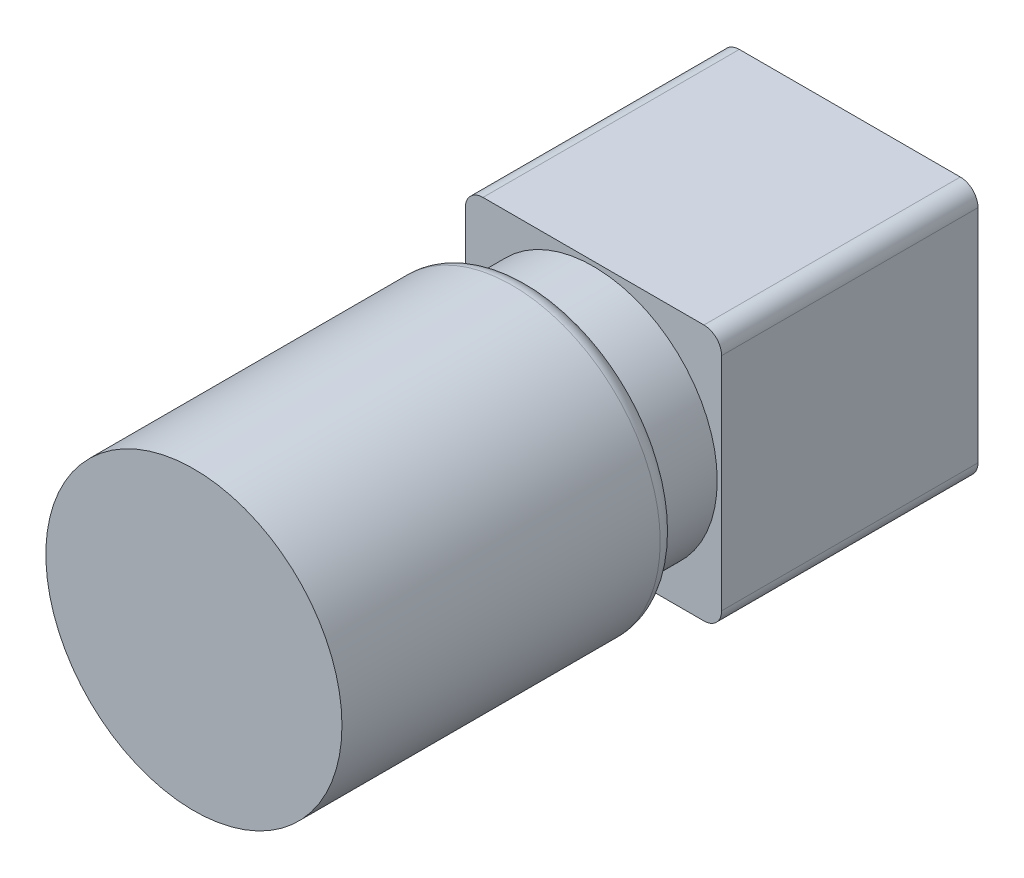
SolidWorks part; units mm, degrees
ref_plane "前视基准面" through (0, 0, 0) normal (0, 0, 1) x (1, 0, 0)
ref_plane "上视基准面" through (0, 0, 0) normal (0, 1, 0) x (1, 0, 0)
ref_plane "右视基准面" through (0, 0, 0) normal (1, 0, 0) x (0, 0, -1)
sketch "草图1" plane through (0, 0, 0) normal (0, 0, 1) x (1, 0, 0)
  line L1 (14.5, -14.5) -> (-14.5, -14.5)
  line L2 (14.5, -14.5) -> (14.5, 14.5)
  line L3 (14.5, 14.5) -> (-14.5, 14.5)
  line L4 (-14.5, -14.5) -> (-14.5, 14.5)
  line L5 (14.5, -14.5) -> (-14.5, 14.5) construction
  line L6 (14.5, 14.5) -> (-14.5, -14.5) construction
  point P0 (0, 0)
  dimension "D1" = 29
  dimension "D2" = 29
extrude "凸台-拉伸1" add sketch "草图1" along normal blind 29
sketch "草图2" plane through (0, 0, 29) normal (0, 0, 1) x (1, 0, 0)
  circle A0 centre (0, 0) radius 14
  dimension "D1" = 28
extrude "凸台-拉伸2" add sketch "草图2" along normal blind 7.2
sketch "草图3" plane through (0, -14.5, 0) normal (0, -1, 0) x (-1, 0, 0)
  line L0 (0, -29) -> (0, 0) construction
  line L2 (14.5, -29) -> (-14.5, -29) construction
  point P6 (0, -14.5)
hole_wizard "M3 螺纹孔1" positions "草图4" profile "草图5" tap size "M3" standard "GB"
sketch "草图4" plane through (0, -14.5, 0) normal (0, -1, 0) x (-1, 0, 0)
  line L0 (14.5, -29) -> (-14.5, -29) construction
  line L3 (0, -29) -> (0, 0) construction
  point P0 (10, -25.5)
  point P24 (-10, -25.5)
  dimension "D1" = 3.5
  dimension "D2" = 10
  dimension "D3" = 3.5
  dimension "D4" = 10
sketch "草图5" plane through (-10, -14.5, 25.5) normal (1, 0, 0) x (0, 0, -1)
  line L0 (0, 0) -> (0, 8.2511)
  line L1 (0, 8.2511) -> (1.25, 7.5)
  line L2 (1.25, 7.5) -> (1.25, 0)
  line L5 (1.25, 0) -> (0, 0)
  line L10 (0, 8.2511) -> (-1.25, 7.5) construction
  line L11 (0, -6.35) -> (0, 107.95) construction
  dimension "螺纹孔钻头直径" = 2.5
  dimension "螺纹孔钻头深度" = 7.5
  dimension "导头角度" = 118
cosmetic thread "孔螺蚊线1" parameters "D1"=6, "D2"=3
cosmetic thread "孔螺蚊线2" parameters "D1"=6, "D2"=3
sketch "草图6" plane through (0, 0, 36.2) normal (0, 0, 1) x (1, 0, 0)
  circle A0 centre (0, 0) radius 16.75
  dimension "D1" = 33.5
extrude "凸台-拉伸3" add sketch "草图6" along normal blind 38
fillet "圆角1" radius 2 5 edges at (16.75, 0, 36.2) (-14.5, 14.5, 14.5) (-14.5, -14.5, 14.5) (14.5, 14.5, 14.5) (14.5, -14.5, 14.5)
sketch "草图7" plane through (0, 0, 0) normal (0, 0, -1) x (-1, 0, 0)
  line L0 (0, 0) -> (0, 15.0455) construction
  line L1 (11, 7) -> (-11, 7)
  line L2 (11, 7) -> (11, 11)
  line L3 (11, 11) -> (-11, 11)
  line L4 (-11, 7) -> (-11, 11)
  line L5 (11, 7) -> (-11, 11) construction
  line L6 (11, 11) -> (-11, 7) construction
  line L7 (-12.5, 14.5) -> (12.5, 14.5) construction
  point P0 (0, 9)
  dimension "D1" = 22
  dimension "D2" = 4
  dimension "D3" = 3.5
extrude "凸台-拉伸4" add sketch "草图7" along normal blind 3.5
fillet "圆角2" radius 2 4 edges at (-11, 7, -1.75) (-11, 11, -1.75) (11, 7, -1.75) (11, 11, -1.75)
